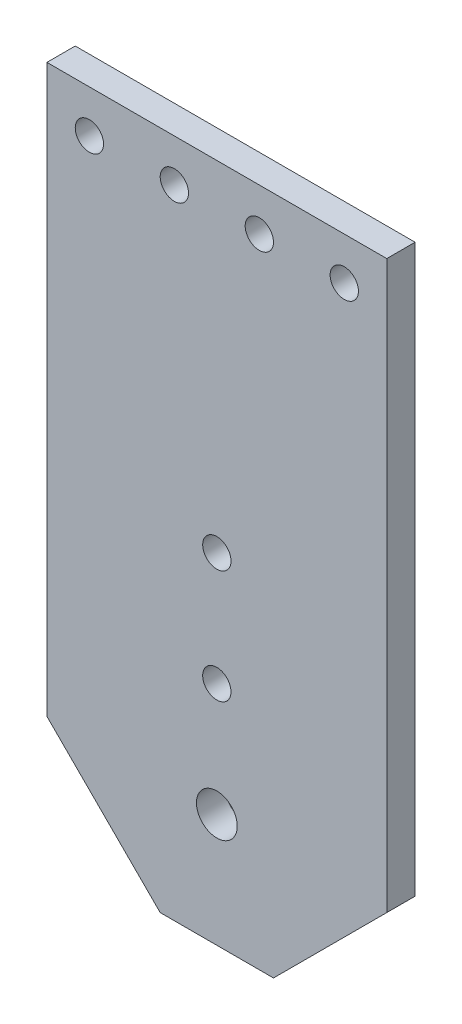
SolidWorks part; units mm, degrees
ref_plane "Front Plane" through (0, 0, 0) normal (0, 0, 1) x (1, 0, 0)
ref_plane "Top Plane" through (0, 0, 0) normal (0, 1, 0) x (1, 0, 0)
ref_plane "Right Plane" through (0, 0, 0) normal (1, 0, 0) x (0, 0, -1)
sketch "Sketch1" plane through (0, 0, 0) normal (0, 0, 1) x (1, 0, 0)
  line L0 (-19.05, 4.7625) -> (-19.05, -58.7375)
  line L5 (19.05, 4.7625) -> (19.05, -58.7375)
  line L6 (19.05, -58.7375) -> (6.35, -71.4375)
  line L7 (-6.35, -71.4375) -> (6.35, -71.4375)
  line L10 (-19.05, -58.7375) -> (-6.35, -71.4375)
  line L11 (-19.05, 4.7625) -> (19.05, 4.7625)
  circle A0 centre (4.7625, 0) radius 1.5875
  circle A1 centre (-4.7625, 0) radius 1.5875
  circle A6 centre (0, -58.7375) radius 2.286
  circle A7 centre (14.2875, 0) radius 1.5875
  circle A8 centre (-14.2875, 0) radius 1.5875
  circle A9 centre (0, -46.0375) radius 1.5875
  circle A10 centre (0, -33.3375) radius 1.5875
  point P0 (0, 0)
  point P11 (0, -71.4375)
extrude "Boss-Extrude2" add sketch "Sketch1" along normal blind 3.175
